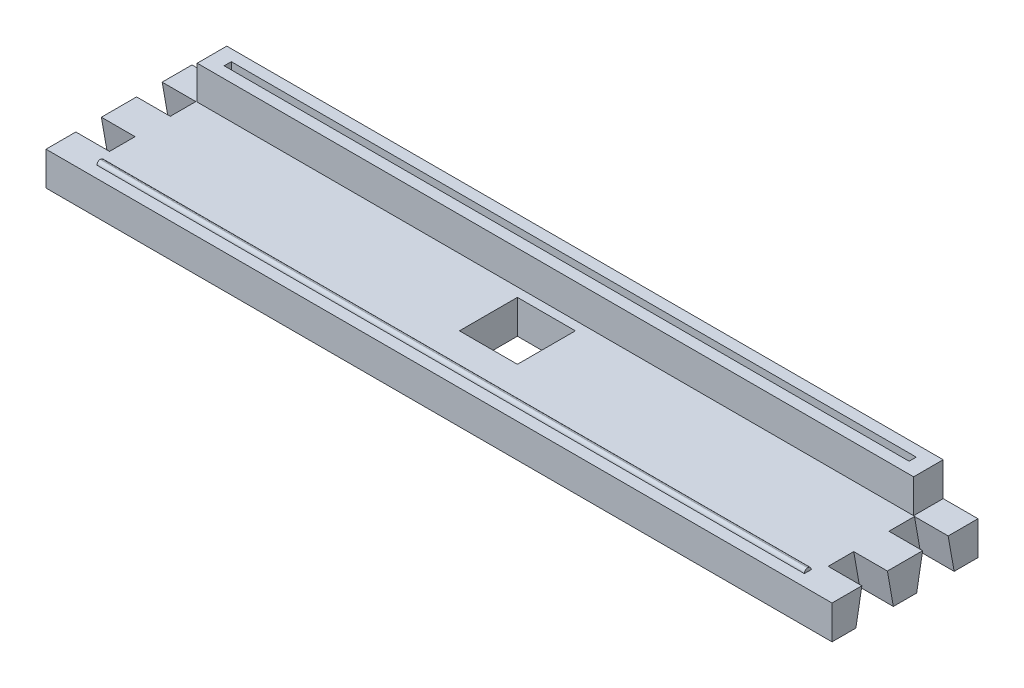
SolidWorks part; units mm, degrees
note: The reader was unsure of these and kept them because the rebuilt part matched: shared geometry of "Sketch2<4>", "Sketch2<7>".
ref_plane "Front Plane" through (0, 0, 0) normal (0, 0, 1) x (1, 0, 0)
ref_plane "Top Plane" through (0, 0, 0) normal (0, 1, 0) x (1, 0, 0)
ref_plane "Right Plane" through (0, 0, 0) normal (1, 0, 0) x (0, 0, -1)
sketch "Sketch2" plane through (0, 0, 0) normal (0, 1, 0) x (1, 0, 0)
  line L0 (0, 65) -> (0, -65) construction
  line L1 (-350, -65) -> (350, -65)
  line L2 (-350, -65) -> (-350, 65)
  line L3 (-350, 65) -> (350, 65)
  line L4 (350, -65) -> (350, 65)
  line L5 (-350, -65) -> (350, 65) construction
  line L6 (-350, 65) -> (350, -65) construction
  line L7 (-320, 65) -> (-320, 38.442)
  line L8 (-25.815, -21) -> (25.815, -21)
  line L9 (-25.815, -21) -> (-25.815, 30.63)
  line L10 (-25.815, 30.63) -> (25.815, 30.63)
  line L11 (25.815, -21) -> (25.815, 30.63)
  line L12 (-25.815, -21) -> (25.815, 30.63) construction
  line L13 (-25.815, 30.63) -> (25.815, -21) construction
  line L14 (320, 65) -> (320, -65)
  line L15 (-320, 38.442) -> (-320, 15.674)
  line L16 (-315, -54.66) -> (315, -54.66)
  line L17 (-315, -54.66) -> (-315, -48.46)
  line L18 (-315, -48.46) -> (315, -48.46)
  line L19 (315, -54.66) -> (315, -48.46)
  line L20 (-320, 15.674) -> (-320, -15.674)
  line L21 (-320, -15.674) -> (-320, -38.442)
  line L22 (-320, -38.442) -> (-320, -65)
  line L23 (-320, 38.442) -> (-350, 38.442)
  line L24 (-320, 15.674) -> (-350, 15.674)
  line L25 (-320, -15.674) -> (-350, -15.674)
  line L26 (-320, -38.442) -> (-350, -38.442)
  line L27 (320, -38.442) -> (350, -38.442)
  line L28 (320, -15.674) -> (350, -15.674)
  line L29 (320, 15.674) -> (350, 15.674)
  line L30 (320, 38.442) -> (350, 38.442)
  line L32 (-305, 48.65) -> (305, 48.65)
  line L33 (-305, 48.65) -> (-305, 55)
  line L34 (-305, 55) -> (305, 55)
  line L35 (305, 48.65) -> (305, 55)
  line L36 (-305, 48.65) -> (305, 55) construction
  line L37 (-305, 55) -> (305, 48.65) construction
  line L38 (-319, 38.65) -> (319, 38.65)
  line L39 (-319, 38.65) -> (-319, 65)
  line L40 (-319, 65) -> (319, 65)
  line L41 (319, 38.65) -> (319, 65)
  line L42 (-319, 38.65) -> (319, 65) construction
  line L43 (-319, 65) -> (319, 38.65) construction
  point P0 (0, 0)
  point P8 (0, 4.815)
  point P37 (0, 51.825)
  point P39 (0, 51.825)
  dimension "D1" = 700
  dimension "D2" = 130
  dimension "D3" = 51.63
  dimension "D4" = 44
  dimension "D5" = 10.34
  dimension "D6" = 6.2
  dimension "D7" = 34.37
  dimension "D8" = 30
  dimension "D9" = 26.558
  dimension "D10" = 31.348
  dimension "D11" = 22.768
  dimension "D12" = 5
  dimension "D13" = 5
  dimension "D14" = 610
  dimension "D15" = 10
  dimension "D16" = 640
  dimension "D17" = 6.35
  dimension "D18" = 1
extrude "Boss-Extrude1" add sketch "Sketch2" against normal blind 30
extrude "Boss-Extrude3" add sketch "Sketch2<4>" along normal blind 3 contours L16 L19 L18 L17
sketch "Sketch2<4>" plane through (0, 0, 0) normal (0, 1, 0) x (1, 0, 0) same geometry as "Sketch2"
fillet "Fillet2" radius 3 2 edges at (0, 3, 48.46) (0, 3, 54.66)
chamfer "Chamfer1" distance 30 angle 10 4 edges at (-335, -30, 15.674) (-335, -30, -38.442) (335, -30, -15.674) (335, -30, 38.442)
chamfer "Chamfer2" distance 30 angle 10 4 edges at (-335, -30, 38.442) (-335, -30, -15.674) (335, -30, -38.442) (335, -30, 15.674)
extrude "Boss-Extrude5" add sketch "Sketch2<7>" along normal blind 30 contours L38 L41 L3 L39 L35 L32 L33 L34
sketch "Sketch2<7>" plane through (0, 0, 0) normal (0, 1, 0) x (1, 0, 0) same geometry as "Sketch2"
